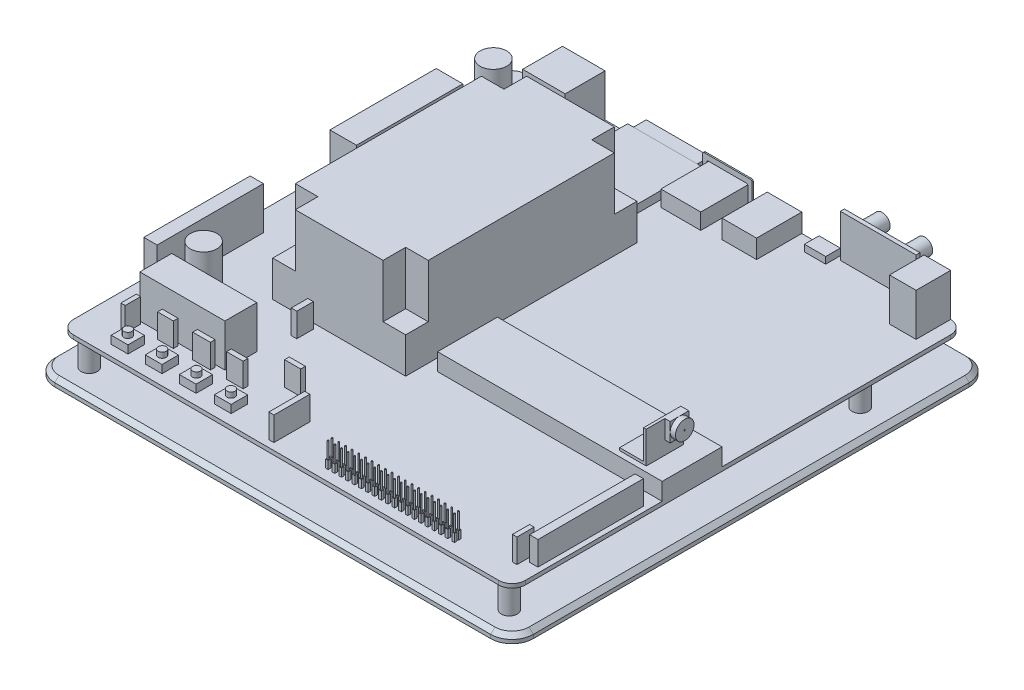
SolidWorks part; units mm, degrees
ref_plane "Plano frontal" through (0, 0, 0) normal (0, 0, 1) x (1, 0, 0)
ref_plane "Plano superior" through (0, 0, 0) normal (0, 1, 0) x (1, 0, 0)
ref_plane "Plano direito" through (0, 0, 0) normal (1, 0, 0) x (0, 0, -1)
sketch "Esboço1" plane through (0, 0, 0) normal (0, 1, 0) x (1, 0, 0)
  line L1 (82, -90) -> (-82, -90)
  line L2 (90, -82) -> (90, 82)
  line L3 (82, 90) -> (-82, 90)
  line L4 (-90, -82) -> (-90, 82)
  line L5 (90, -90) -> (-90, 90) construction
  line L6 (90, 90) -> (-90, -90) construction
  arc A0 (82, -90) -> (90, -82) centre (82, -82) ccw
  arc A1 (-82, -90) -> (-90, -82) centre (-82, -82) cw
  arc A2 (90, 82) -> (82, 90) centre (82, 82) ccw
  arc A3 (-82, 90) -> (-90, 82) centre (-82, 82) ccw
  point P0 (0, 0)
  dimension "D3" = 8
  dimension "D1" = 180
  dimension "D2" = 180
extrude "Ressalto-extrusão1" add sketch "Esboço1" along normal blind 3
sketch "Esboço2" plane through (0, 0, 0) normal (0, -1, 0) x (-1, 0, 0)
  line L0 (82, -90) -> (-82, -90) construction
  line L1 (90, 82) -> (90, -82) construction
  line L2 (0, 0) -> (-90, 0) construction
  line L3 (-90, -82) -> (-90, 82) construction
  line L4 (0, 0) -> (0, -90) construction
  circle A0 centre (79, -62) radius 3.5
  circle A1 centre (-79, -62) radius 3.5
  circle A2 centre (-79, 62) radius 3.5
  circle A3 centre (79, 62) radius 3.5
  dimension "D1" = 7
  dimension "D2" = 28
  dimension "D3" = 11
extrude "Ressalto-extrusão2" add sketch "Esboço2" along normal blind 5
sketch "Esboço3" plane through (0, 3, 0) normal (0, 1, 0) x (1, 0, 0)
  line L0 (90, -82) -> (90, 82) construction
  line L1 (-82, -90) -> (82, -90) construction
  line L2 (-90, 82) -> (-90, -82) construction
  line L3 (82, 90) -> (-82, 90) construction
  circle A0 centre (-79, -80) radius 3
  circle A1 centre (-79, 75) radius 3
  circle A2 centre (79, 52) radius 3
  circle A3 centre (79, -80) radius 3
  dimension "D1" = 6
  dimension "D3" = 11
  dimension "D5" = 10
  dimension "D6" = 38
  dimension "D2" = 10
  dimension "D4" = 11
  dimension "D7" = 15
extrude "Ressalto-extrusão3" add sketch "Esboço3" along normal blind 11
sketch "Esboço4" plane through (0, 14, 0) normal (0, 1, 0) x (1, 0, 0)
  line L1 (-80, 85) -> (80, 85)
  line L2 (-85, 80) -> (-85, -80)
  line L3 (-80, -85) -> (80, -85)
  line L4 (85, 80) -> (85, -80)
  line L5 (-85, 85) -> (85, -85) construction
  line L6 (-85, -85) -> (85, 85) construction
  arc A1 (80, -85) -> (85, -80) centre (80, -80) ccw
  arc A2 (-85, -80) -> (-80, -85) centre (-80, -80) ccw
  arc A3 (80, 85) -> (85, 80) centre (80, 80) cw
  arc A4 (-80, 85) -> (-85, 80) centre (-80, 80) ccw
  point P0 (0, 0)
  dimension "D3" = 5
  dimension "D1" = 170
  dimension "D2" = 170
extrude "Ressalto-extrusão4" add sketch "Esboço4" along normal blind 1.5
sketch "Esboço5" plane through (0, 15.5, 0) normal (0, 1, 0) x (1, 0, 0)
  line L0 (-80, -85) -> (80, -85) construction
  line L1 (-54, 51) -> (-4, 51)
  line L2 (-54, 51) -> (-54, -36)
  line L3 (-54, -36) -> (-4, -36)
  line L4 (-4, 51) -> (-4, -36)
  line L5 (-54, 51) -> (-4, -36) construction
  line L6 (-54, -36) -> (-4, 51) construction
  line L7 (-85, 80) -> (-85, -80) construction
  point P0 (-29, 7.5)
  dimension "D1" = 50
  dimension "D2" = 87
  dimension "D3" = 49
  dimension "D4" = 31
extrude "Ressalto-extrusão5" add sketch "Esboço5" along normal blind 33.5
sketch "Esboço6" plane through (0, 49, 0) normal (0, 1, 0) x (1, 0, 0)
  line L0 (-54, 7.5) -> (-4, 7.5) construction
  line L1 (-54, -36) -> (-45.5, -36)
  line L2 (-54, -36) -> (-54, -27.5)
  line L3 (-54, -27.5) -> (-45.5, -27.5)
  line L4 (-45.5, -36) -> (-45.5, -27.5)
  line L5 (-54, 51) -> (-54, -36) construction
  line L6 (-4, -36) -> (-4, 51) construction
  line L7 (-29, 51) -> (-29, -36) construction
  line L8 (-4, 51) -> (-54, 51) construction
  line L9 (-54, -36) -> (-4, -36) construction
  line L10 (-12.5, -36) -> (-12.5, -27.5)
  line L11 (-4, -36) -> (-12.5, -36)
  line L12 (-4, -36) -> (-4, -27.5)
  line L13 (-4, -27.5) -> (-12.5, -27.5)
  line L14 (-4, 42.5) -> (-12.5, 42.5)
  line L15 (-4, 51) -> (-4, 42.5)
  line L16 (-4, 51) -> (-12.5, 51)
  line L17 (-12.5, 51) -> (-12.5, 42.5)
  line L18 (-45.5, 51) -> (-45.5, 42.5)
  line L19 (-54, 42.5) -> (-45.5, 42.5)
  line L20 (-54, 51) -> (-54, 42.5)
  line L21 (-54, 51) -> (-45.5, 51)
  dimension "D1" = 8.5
  dimension "D2" = 8.5
extrude "Corte-extrusão1" cut sketch "Esboço6" against normal blind 20
sketch "Esboço7" plane through (0, 15.5, 0) normal (0, 1, 0) x (1, 0, 0)
  line L0 (-30.95, -74.8) -> (-24.65, -74.8)
  line L1 (-69.75, -74.8) -> (-63.45, -74.8)
  line L2 (-69.75, -74.8) -> (-69.75, -81)
  line L3 (-69.75, -81) -> (-63.45, -81)
  line L4 (-63.45, -74.8) -> (-63.45, -81)
  line L5 (-69.75, -74.8) -> (-63.45, -81) construction
  line L6 (-69.75, -81) -> (-63.45, -74.8) construction
  line L7 (-80, -85) -> (80, -85) construction
  line L8 (-85, 80) -> (-85, -80) construction
  line L9 (-56.95, -74.8) -> (-50.65, -74.8)
  line L10 (-56.95, -74.8) -> (-56.95, -81)
  line L11 (-56.95, -81) -> (-50.65, -81)
  line L12 (-50.65, -74.8) -> (-50.65, -81)
  line L13 (-56.95, -74.8) -> (-50.65, -81) construction
  line L14 (-56.95, -81) -> (-50.65, -74.8) construction
  line L15 (-44.15, -74.8) -> (-37.85, -74.8)
  line L16 (-44.15, -74.8) -> (-44.15, -81)
  line L17 (-44.15, -81) -> (-37.85, -81)
  line L18 (-37.85, -74.8) -> (-37.85, -81)
  line L19 (-44.15, -74.8) -> (-37.85, -81) construction
  line L20 (-44.15, -81) -> (-37.85, -74.8) construction
  line L21 (-30.95, -74.8) -> (-30.95, -81)
  line L22 (-30.95, -81) -> (-24.65, -81)
  line L23 (-24.65, -74.8) -> (-24.65, -81)
  line L24 (-30.95, -74.8) -> (-24.65, -81) construction
  line L25 (-30.95, -81) -> (-24.65, -74.8) construction
  point P0 (-66.6, -77.9)
  point P10 (-27.8, -77.9)
  point P11 (-53.8, -77.9)
  point P16 (-41, -77.9)
  dimension "D1" = 6.2
  dimension "D2" = 6.3
  dimension "D3" = 4
  dimension "D4" = 15.25
  dimension "D5" = 3
  dimension "D6" = 6.5
  dimension "D8" = 6.9
  dimension "D7" = 2
extrude "Ressalto-extrusão6" add sketch "Esboço7" along normal blind 3
sketch "Esboço8" plane through (0, 18.5, 0) normal (0, 1, 0) x (1, 0, 0)
  line L0 (-63.45, -81) -> (-63.45, -74.8) construction
  line L2 (-69.75, -81) -> (-63.45, -81) construction
  line L3 (-24.65, -81) -> (-24.65, -74.8) construction
  line L4 (-24.65, -74.8) -> (-30.95, -74.8) construction
  circle A0 centre (-66.6, -77.9) radius 1.5
  circle A1 centre (-53.7, -77.9) radius 1.5
  circle A2 centre (-40.8, -77.9) radius 1.5
  circle A3 centre (-27.75, -77.95) radius 1.5
  point P6 (-66.6, -81)
  dimension "D1" = 3.15
  dimension "D2" = 3.1
  dimension "D3" = 3
  dimension "D5" = 3
  dimension "D6" = 3.1
  dimension "D7" = 3.15
  dimension "D8" = 12.9
  dimension "D4" = 3
extrude "Ressalto-extrusão7" add sketch "Esboço8" along normal blind 2
sketch "Esboço9" plane through (0, 15.5, 0) normal (0, 1, 0) x (1, 0, 0)
  line L0 (-80, -85) -> (80, -85) construction
  line L1 (10.85, -80) -> (11.85, -80)
  line L2 (10.85, -80) -> (10.85, -81)
  line L3 (10.85, -81) -> (11.85, -81)
  line L4 (11.85, -80) -> (11.85, -81)
  line L5 (10.85, -80) -> (11.85, -81) construction
  line L6 (10.85, -81) -> (11.85, -80) construction
  line L7 (-24.65, -81) -> (-24.65, -74.8) construction
  point P0 (11.35, -80.5)
  dimension "D1" = 1
  dimension "D2" = 4
  dimension "D3" = 35.5
extrude "Ressalto-extrusão8" add sketch "Esboço9" along normal blind 3
sketch "Esboço10" plane through (0, 18.5, 0) normal (0, 1, 0) x (1, 0, 0)
  line L1 (11.35, -80) -> (11.35, -80.5) construction
  line L2 (11.85, -80) -> (10.85, -80) construction
  line L3 (11.35, -80.5) -> (11.85, -80.5) construction
  line L4 (11.85, -81) -> (11.85, -80) construction
  circle A0 centre (11.35, -80.5) radius 0.25
  dimension "D1" = 0.5
extrude "Ressalto-extrusão9" add sketch "Esboço10" along normal blind 6
pattern_linear "Padrão linear1" count 20 spacing 2.5 along (1, 0, 0) count 2 spacing 1.5 along (0, 0, -1) of "Ressalto-extrusão8", "Ressalto-extrusão9"
sketch "Esboço11" plane through (0, 15.5, 0) normal (0, 1, 0) x (1, 0, 0)
  line L0 (80, 85) -> (-80, 85) construction
  line L1 (-71.9966, -56) -> (-39.9966, -56)
  line L2 (-71.9966, -56) -> (-71.9966, -68)
  line L3 (-71.9966, -68) -> (-39.9966, -68)
  line L4 (-39.9966, -56) -> (-39.9966, -68)
  line L5 (-82.5, -56) -> (-77.5, -56)
  line L6 (-82.5, -56) -> (-82.5, -16)
  line L7 (-82.5, -16) -> (-77.5, -16)
  line L8 (-77.5, -56) -> (-77.5, -16)
  line L9 (-82.5, 54) -> (-72.5, 54)
  line L10 (-82.5, 54) -> (-82.5, 14)
  line L11 (-82.5, 14) -> (-72.5, 14)
  line L12 (-72.5, 54) -> (-72.5, 14)
  line L13 (-66, 85) -> (-50, 85)
  line L14 (-66, 85) -> (-66, 70)
  line L15 (-66, 70) -> (-50, 70)
  line L16 (-50, 85) -> (-50, 70)
  line L17 (-85, 80) -> (-85, -80) construction
  line L18 (-80, -85) -> (80, -85) construction
  line L19 (80, 85) -> (70, 85)
  line L20 (80, 85) -> (80, 72)
  line L21 (80, 72) -> (70, 72)
  line L22 (70, 85) -> (70, 72)
  line L23 (68.5, 85) -> (40, 85)
  line L24 (68.5, 85) -> (68.5, 83.5)
  line L25 (68.5, 83.5) -> (40, 83.5)
  line L26 (40, 85) -> (40, 83.5)
  circle A0 centre (-70, -46) radius 5
  circle A1 centre (-75, 68) radius 5
  dimension "D1" = 10
  dimension "D2" = 10
  dimension "D12" = 17
  dimension "D26" = 10
  dimension "D3" = 15
  dimension "D4" = 16
  dimension "D5" = 19
  dimension "D6" = 13
  dimension "D7" = 10
  dimension "D8" = 28.5
  dimension "D9" = 1.5
  dimension "D10" = 1.5
  dimension "D11" = 10
  dimension "D13" = 10
  dimension "D14" = 40
  dimension "D15" = 2.5
  dimension "D16" = 2.5
  dimension "D17" = 5
  dimension "D18" = 29
  dimension "D19" = 30
  dimension "D20" = 40
  dimension "D21" = 7.5
  dimension "D22" = 12
  dimension "D23" = 32
  dimension "D24" = 13.0034
  dimension "D25" = 17
extrude "Ressalto-extrusão10" add sketch "Esboço11" along normal blind 16
sketch "Esboço12" plane through (0, 0, -85) normal (0, 0, -1) x (-1, 0, 0)
  line L0 (-68.5, 31.5) -> (-40, 31.5) construction
  line L1 (-62.25, 26.5) -> (-68.5, 26.5) construction
  line L2 (-68.5, 31.5) -> (-68.5, 15.5) construction
  line L3 (-46.25, 26.5) -> (-40, 26.5) construction
  line L4 (-40, 31.5) -> (-40, 15.5) construction
  circle A0 centre (-62.25, 26.5) radius 3
  circle A1 centre (-46.25, 26.5) radius 3
  dimension "D1" = 6
  dimension "D2" = 6
  dimension "D3" = 5
  dimension "D4" = 16
extrude "Ressalto-extrusão11" add sketch "Esboço12" along normal blind 8
sketch "Esboço13" plane through (0, 15.5, 0) normal (0, 1, 0) x (1, 0, 0)
  line L0 (-69.75, -74.8) -> (-69.75, -81) construction
  line L1 (-70.7943, -68.907) -> (-72.4259, -68.907)
  line L2 (-70.7943, -68.907) -> (-70.7943, -74.6918)
  line L3 (-70.7943, -74.6918) -> (-72.4259, -74.6918)
  line L4 (-72.4259, -68.907) -> (-72.4259, -74.6918)
  line L5 (-62.6363, -68.907) -> (-56.7033, -68.907)
  line L6 (-62.6363, -68.907) -> (-62.6363, -70.6869)
  line L7 (-62.6363, -70.6869) -> (-56.7033, -70.6869)
  line L8 (-56.7033, -68.907) -> (-56.7033, -70.6869)
  line L9 (-49.4353, -68.907) -> (-42.7606, -68.907)
  line L10 (-49.4353, -68.907) -> (-49.4353, -70.6869)
  line L11 (-49.4353, -70.6869) -> (-42.7606, -70.6869)
  line L12 (-42.7606, -68.907) -> (-42.7606, -70.6869)
  line L13 (-36.6792, -68.907) -> (-30.4495, -68.907)
  line L14 (-36.6792, -68.907) -> (-36.6792, -70.6869)
  line L15 (-36.6792, -70.6869) -> (-30.4495, -70.6869)
  line L16 (-30.4495, -68.907) -> (-30.4495, -70.6869)
  line L17 (-9.0905, -68.907) -> (-7.1623, -68.907)
  line L18 (-9.0905, -68.907) -> (-9.0905, -82.4047)
  line L19 (-9.0905, -82.4047) -> (-7.1623, -82.4047)
  line L20 (-7.1623, -68.907) -> (-7.1623, -82.4047)
  line L21 (-23.1815, -60.6008) -> (-17.1002, -60.6008)
  line L22 (-23.1815, -60.6008) -> (-23.1815, -62.3807)
  line L23 (-23.1815, -62.3807) -> (-17.1002, -62.3807)
  line L24 (-17.1002, -60.6008) -> (-17.1002, -62.3807)
  line L25 (-38.7558, -38.0552) -> (-36.6792, -38.0552)
  line L26 (-38.7558, -38.0552) -> (-38.7558, -44.2849)
  line L27 (-38.7558, -44.2849) -> (-36.6792, -44.2849)
  line L28 (-36.6792, -38.0552) -> (-36.6792, -44.2849)
  line L29 (83.0751, -73.3111) -> (79.9494, -73.3111)
  line L30 (83.0751, -73.3111) -> (83.0751, -33.6552)
  line L31 (83.0751, -33.6552) -> (79.9494, -33.6552)
  line L32 (79.9494, -73.3111) -> (79.9494, -33.6552)
  line L33 (78.3022, -70.0067) -> (76.6024, -70.0067)
  line L34 (78.3022, -70.0067) -> (78.3022, -76.444)
  line L35 (78.3022, -76.444) -> (76.6024, -76.444)
  line L36 (76.6024, -70.0067) -> (76.6024, -76.444)
  line L37 (-63.45, -74.8) -> (-69.75, -74.8) construction
  dimension "D1" = 7.1137
  dimension "D2" = 13.0467
  dimension "D3" = 20.3147
  dimension "D4" = 26.9894
  dimension "D5" = 30.9942
  dimension "D6" = 33.0708
  dimension "D7" = 39.3005
  dimension "D8" = 46.5685
  dimension "D9" = 52.6498
  dimension "D10" = 60.6595
  dimension "D11" = 62.5877
  dimension "D12" = 146.3524
  dimension "D13" = 148.0522
  dimension "D14" = 149.6994
  dimension "D15" = 152.8251
  dimension "D16" = 1.0443
  dimension "D17" = 2.6759
  dimension "D18" = 0.1082
  dimension "D19" = 1.4889
  dimension "D20" = 4.1131
  dimension "D21" = 4.7933
  dimension "D22" = 5.893
  dimension "D23" = 12.4193
  dimension "D24" = 30.5151
  dimension "D27" = 41.1448
  dimension "D28" = 1.644
  dimension "D29" = 7.6047
extrude "Ressalto-extrusão12" add sketch "Esboço13" along normal blind 9
sketch "Esboço14" plane through (0, 15.5, 0) normal (0, 1, 0) x (1, 0, 0)
  line L0 (85, -80) -> (85, 80) construction
  line L1 (85, -28.5) -> (0.5, -28.5)
  line L2 (85, -28.5) -> (85, -6)
  line L3 (85, -6) -> (0.5, -6)
  line L4 (0.5, -28.5) -> (0.5, -6)
  line L5 (-80, -85) -> (80, -85) construction
  dimension "D1" = 56.5
  dimension "D2" = 84.5
  dimension "D3" = 22.5
extrude "Ressalto-extrusão13" add sketch "Esboço14" along normal blind 6.5
sketch "Esboço15" plane through (0, 22, 0) normal (0, 1, 0) x (1, 0, 0)
  line L0 (85, -28.5) -> (85, -6) construction
  line L1 (77, -12.5) -> (76, -12.5)
  line L2 (77, -12.5) -> (77, -26.5)
  line L3 (77, -26.5) -> (76, -26.5)
  line L4 (76, -12.5) -> (76, -26.5)
  line L5 (0.5, -28.5) -> (85, -28.5) construction
  dimension "D1" = 14
  dimension "D2" = 1
  dimension "D3" = 8
  dimension "D4" = 2
extrude "Ressalto-extrusão14" add sketch "Esboço15" along normal blind 12
sketch "Esboço16" plane through (76, 0, 0) normal (-1, 0, 0) x (0, 0, 1)
  line L0 (26.5, 34) -> (26.5, 22) construction
  line L1 (12.5, 22) -> (26.5, 22)
  line L2 (12.5, 22) -> (12.5, 23)
  line L3 (12.5, 23) -> (26.5, 23)
  line L4 (26.5, 22) -> (26.5, 23)
  dimension "D1" = 1
extrude "Ressalto-extrusão15" add sketch "Esboço16" along normal blind 9
sketch "Esboço17" plane through (77, 0, 0) normal (1, 0, 0) x (0, 0, -1)
  line L1 (-12.5, 34) -> (-19.5, 34)
  line L2 (-12.5, 34) -> (-12.5, 27)
  line L3 (-12.5, 27) -> (-19.5, 27)
  line L4 (-19.5, 34) -> (-19.5, 27)
  dimension "D1" = 7
  dimension "D2" = 7
extrude "Ressalto-extrusão16" add sketch "Esboço17" along normal blind 2
sketch "Esboço18" plane through (79, 0, 0) normal (1, 0, 0) x (0, 0, -1)
  line L0 (-16, 34) -> (-16, 30.5) construction
  line L1 (-12.5, 34) -> (-19.5, 34) construction
  line L2 (-16, 30.5) -> (-12.5, 30.5) construction
  line L3 (-12.5, 27) -> (-12.5, 34) construction
  circle A0 centre (-16, 30.5) radius 3.5
  dimension "D1" = 7
extrude "Ressalto-extrusão17" add sketch "Esboço18" along normal blind 2
sketch "Esboço19" plane through (81, 0, 0) normal (1, 0, 0) x (0, 0, -1)
  circle A0 centre (-16, 30.5) radius 0.35
  circle A1 centre (-16, 30.5) radius 0.25
  dimension "D1" = 0.5
  dimension "D2" = 0.1
extrude "Corte-extrusão2" cut sketch "Esboço19" against normal blind 0.2
sketch "Esboço20" plane through (0, 15.5, 0) normal (0, 1, 0) x (1, 0, 0)
  line L0 (40, 85) -> (-50, 85) construction
  line L1 (-41.5, 85) -> (-13.5, 85)
  line L2 (-41.5, 85) -> (-41.5, 56)
  line L3 (-41.5, 56) -> (-13.5, 56)
  line L4 (-13.5, 85) -> (-13.5, 56)
  line L5 (-50, 70) -> (-50, 85) construction
  line L6 (-39.5, 85) -> (-15.5, 85)
  line L7 (-39.5, 85) -> (-39.5, 90)
  line L8 (-39.5, 90) -> (-15.5, 90)
  line L9 (-15.5, 85) -> (-15.5, 90)
  point P12 (-27.5, 90)
  point P13 (-27.5, 85)
  dimension "D1" = 8.5
  dimension "D2" = 28
  dimension "D3" = 29
  dimension "D4" = 5
  dimension "D5" = 24
extrude "Ressalto-extrusão18" add sketch "Esboço20" along normal blind 3 contours L1 L9 L8 L7 | L4 L1 L2 L3
sketch "Esboço21" plane through (0, 0, -90) normal (0, 0, -1) x (-1, 0, 0)
  line L0 (15.5, 18.5) -> (15.5, 15.5) construction
  line L1 (39.5, 15.5) -> (15.5, 15.5)
  line L2 (39.5, 15.5) -> (39.5, 15.7)
  line L3 (39.5, 15.7) -> (15.5, 15.7)
  line L4 (15.5, 15.5) -> (15.5, 15.7)
  line L5 (39.5, 17) -> (15.5, 17) construction
  line L6 (39.5, 18.5) -> (39.5, 15.5) construction
  line L7 (15.5, 18.5) -> (15.5, 18.3)
  line L8 (39.5, 18.3) -> (15.5, 18.3)
  line L9 (39.5, 18.5) -> (39.5, 18.3)
  line L10 (39.5, 18.5) -> (15.5, 18.5)
  dimension "D1" = 0.2
extrude "Corte-extrusão3" cut sketch "Esboço21" against normal blind 5
sketch "Esboço22" plane through (0, 15.5, 0) normal (0, 1, 0) x (1, 0, 0)
  line L0 (40, 85) -> (-13.5, 85) construction
  line L1 (-11, 85) -> (4, 85)
  line L2 (-11, 85) -> (-11, 67)
  line L3 (-11, 67) -> (4, 67)
  line L4 (4, 85) -> (4, 67)
  line L5 (-13.5, 85) -> (-13.5, 56) construction
  dimension "D1" = 15
  dimension "D2" = 18
  dimension "D3" = 2.5
extrude "Ressalto-extrusão19" add sketch "Esboço22" along normal blind 6
sketch "Esboço23" plane through (0, 15.5, 0) normal (0, 1, 0) x (1, 0, 0)
  line L0 (40, 85) -> (4, 85) construction
  line L1 (11, 85) -> (24, 85)
  line L2 (11, 85) -> (11, 68)
  line L3 (11, 68) -> (24, 68)
  line L4 (24, 85) -> (24, 68)
  line L5 (4, 67) -> (4, 85) construction
  dimension "D1" = 13
  dimension "D2" = 17
  dimension "D3" = 7
extrude "Ressalto-extrusão20" add sketch "Esboço23" along normal blind 7
sketch "Esboço24" plane through (0, 15.5, 0) normal (0, 1, 0) x (1, 0, 0)
  line L0 (40, 85) -> (24, 85) construction
  line L1 (30.5, 85) -> (38.5, 85)
  line L2 (30.5, 85) -> (30.5, 79.5)
  line L3 (30.5, 79.5) -> (38.5, 79.5)
  line L4 (38.5, 85) -> (38.5, 79.5)
  line L5 (24, 68) -> (24, 85) construction
  dimension "D1" = 8
  dimension "D2" = 5.5
  dimension "D3" = 6.5
extrude "Ressalto-extrusão21" add sketch "Esboço24" along normal blind 2.5
sketch "Esboço25" plane through (0, 0, -85) normal (0, 0, -1) x (-1, 0, 0)
  line L0 (-3.5, 20) -> (10.5, 20)
  line L1 (10.5, 20) -> (10.5, 17)
  line L2 (10.5, 17) -> (9, 15.5)
  line L3 (9, 15.5) -> (-2, 15.5)
  line L4 (-2, 15.5) -> (-3.5, 17)
  line L5 (-3.5, 17) -> (-3.5, 20)
  line L6 (10.5, 20) -> (11, 20) construction
  line L7 (11, 21.5) -> (11, 15.5) construction
  line L8 (-3.5, 20) -> (-4, 20) construction
  line L9 (-4, 21.5) -> (-4, 15.5) construction
  line L10 (3.5, 20) -> (3.5, 21.5) construction
  line L11 (-4, 21.5) -> (11, 21.5) construction
  line L12 (3.5, 15.5) -> (3.5, 14) construction
  line L13 (-80, 14) -> (80, 14) construction
  line L14 (-1.5, 17.5) -> (-3.5, 17.5) construction
  line L15 (-1.5, 18) -> (8.5, 18)
  line L16 (-1.5, 18) -> (-1.5, 17.5)
  line L17 (-1.5, 17.5) -> (8.5, 17.5)
  line L18 (8.5, 18) -> (8.5, 17.5)
  line L19 (8.5, 17.5) -> (10.5, 17.5) construction
  point P28 (3.5, 15.5)
  point P29 (3.5, 20)
  dimension "D1" = 14
  dimension "D2" = 3
  dimension "D3" = 4.5
  dimension "D4" = 10
  dimension "D5" = 0.5
  dimension "D6" = 0.5
extrude "Corte-extrusão4" cut sketch "Esboço25" against normal blind 8.5
sketch "Esboço26" plane through (0, 0, -85) normal (0, 0, -1) x (-1, 0, 0)
  line L0 (-4.2, 15.5) -> (-4.2, 21.5)
  line L1 (-85, 15.5) -> (-0.5, 15.5) construction
  line L2 (-3.7, 22) -> (10.7, 22)
  line L3 (11.2, 21.5) -> (11.2, 15.5)
  line L4 (11, 15.5) -> (13.5, 15.5) construction
  line L5 (11.2, 15.5) -> (12.75, 15.5)
  line L6 (4, 15.5) -> (54, 15.5) construction
  line L7 (12.75, 15.5) -> (12.75, 23.5)
  line L8 (12.25, 24) -> (-5.25, 24)
  line L9 (-5.75, 23.5) -> (-5.75, 15.5)
  line L10 (-11, 15.5) -> (-4, 15.5) construction
  line L11 (-5.75, 15.5) -> (-4.2, 15.5)
  line L12 (-4, 21.5) -> (-4, 15.5) construction
  line L13 (11, 21.5) -> (11, 15.5) construction
  line L14 (-4, 21.5) -> (11, 21.5) construction
  arc A0 (10.7, 22) -> (11.2, 21.5) centre (10.7, 21.5) cw
  arc A1 (-4.2, 21.5) -> (-3.7, 22) centre (-3.7, 21.5) cw
  arc A2 (12.75, 23.5) -> (12.25, 24) centre (12.25, 23.5) ccw
  arc A3 (-5.25, 24) -> (-5.75, 23.5) centre (-5.25, 23.5) ccw
  point P28 (12.75, 24)
  point P31 (-5.75, 24)
  dimension "D6" = 0.5
  dimension "D1" = 8.5
  dimension "D2" = 18.5
  dimension "D3" = 0.2
  dimension "D4" = 0.2
  dimension "D5" = 0.5
extrude "Ressalto-extrusão22" add sketch "Esboço26" against normal blind 0.5
sketch "Esboço27" plane through (0, 0, -85) normal (0, 0, -1) x (-1, 0, 0)
  line L0 (-24, 22.5) -> (-24, 15.5) construction
  line L1 (-23.8, 22.3) -> (-11.2, 22.3)
  line L2 (-23.8, 22.3) -> (-23.8, 15.7)
  line L3 (-23.8, 15.7) -> (-11.2, 15.7)
  line L4 (-11.2, 22.3) -> (-11.2, 15.7)
  line L5 (-11, 22.5) -> (-11, 15.5) construction
  line L6 (-24, 22.5) -> (-11, 22.5) construction
  line L7 (-85, 15.5) -> (-0.5, 15.5) construction
  line L8 (-22.8, 21.3) -> (-12.2, 21.3)
  line L9 (-12.2, 21.3) -> (-12.2, 19.8)
  line L10 (-12.2, 21.3) -> (-12.2, 16.7) construction
  line L11 (-22.8, 21.3) -> (-22.8, 19.8)
  line L12 (-22.8, 19.8) -> (-12.2, 19.8)
  line L13 (-22.8, 21.3) -> (-22.8, 16.7) construction
  line L14 (-22.8, 16.7) -> (-12.2, 16.7) construction
  dimension "D1" = 0.2
  dimension "D2" = 0.2
  dimension "D3" = 0.2
  dimension "D4" = 0.2
  dimension "D6" = 1.5
  dimension "D5" = 1
extrude "Corte-extrusão5" cut sketch "Esboço27" against normal blind 10
sketch "Esboço28" plane through (0, 0, -85) normal (0, 0, -1) x (-1, 0, 0)
  line L0 (-40, 15.5) -> (-38.5, 15.5) construction
  line L1 (-37.3, 17.8) -> (-31.7, 17.8)
  line L2 (-38.3, 16.8) -> (-38.3, 16.7)
  line L3 (-37.3, 15.7) -> (-31.7, 15.7)
  line L4 (-30.7, 16.8) -> (-30.7, 16.7)
  line L5 (-38.5, 18) -> (-30.5, 18) construction
  line L6 (-38.5, 18) -> (-38.5, 15.5) construction
  line L7 (-30.5, 18) -> (-30.5, 15.5) construction
  arc A0 (-31.7, 15.7) -> (-30.7, 16.7) centre (-31.7, 16.7) ccw
  arc A1 (-31.7, 17.8) -> (-30.7, 16.8) centre (-31.7, 16.8) cw
  arc A2 (-38.3, 16.7) -> (-37.3, 15.7) centre (-37.3, 16.7) ccw
  arc A3 (-37.3, 17.8) -> (-38.3, 16.8) centre (-37.3, 16.8) ccw
  dimension "D5" = 1
  dimension "D1" = 0.2
  dimension "D2" = 0.2
  dimension "D3" = 0.2
  dimension "D4" = 0.2
extrude "Corte-extrusão6" cut sketch "Esboço28" against normal blind 4
chamfer "Chanfro1" distance 1.6 angle 45 8 edges at (90, 3, 0) (87.6569, 3, -87.6569) (87.6569, 3, 87.6569) (0, 3, -90) (0, 3, 90) (-87.6569, 3, -87.6569) (-87.6569, 3, 87.6569) (-90, 3, 0)
